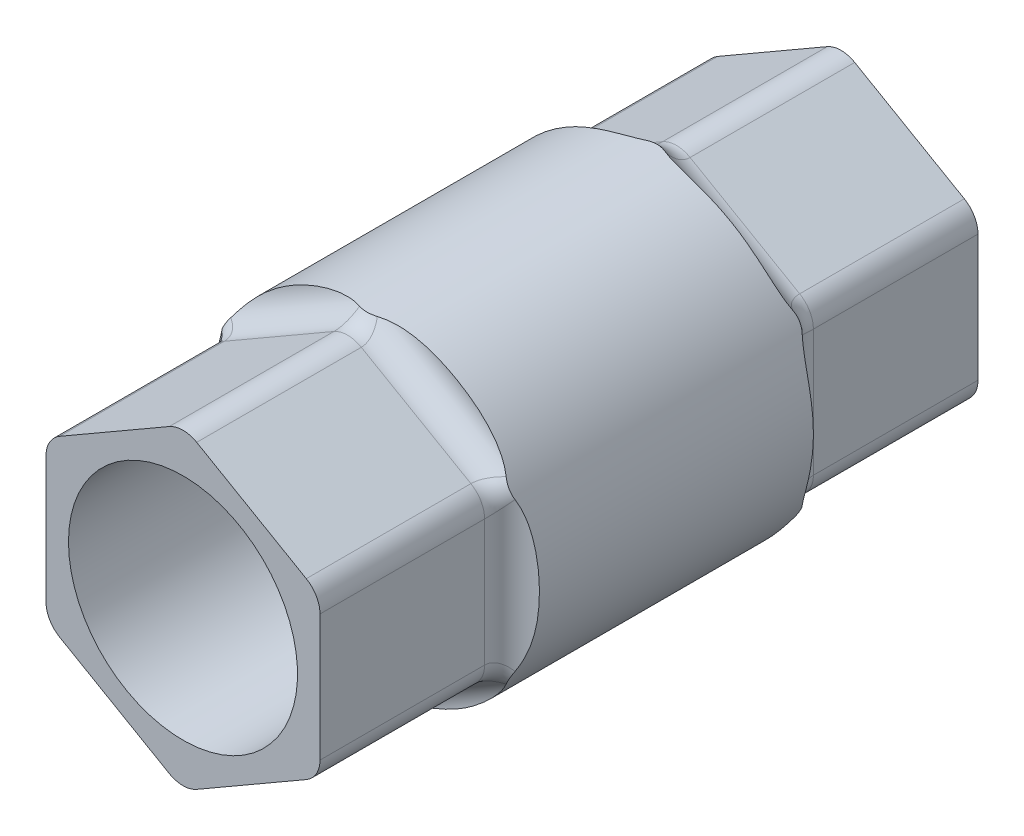
SolidWorks part; units mm, degrees
ref_plane "Front Plane" through (0, 0, 0) normal (0, 0, 1) x (1, 0, 0)
ref_plane "Top Plane" through (0, 0, 0) normal (0, 1, 0) x (1, 0, 0)
ref_plane "Right Plane" through (0, 0, 0) normal (1, 0, 0) x (0, 0, -1)
sketch "Sketch1" plane through (0, 0, 0) normal (0, 0, 1) x (1, 0, 0)
  line L1 (0, 14.6647) -> (-12.7, 7.3323)
  line L2 (-12.7, 7.3323) -> (-12.7, -7.3323)
  line L3 (-12.7, -7.3323) -> (0, -14.6647)
  line L4 (0, -14.6647) -> (12.7, -7.3323)
  line L5 (12.7, -7.3323) -> (12.7, 7.3323)
  line L6 (12.7, 7.3323) -> (0, 14.6647)
  circle A0 centre (0, 0) radius 12.7 construction
  circle A1 centre (0, 0) radius 10.6171
  dimension "D1" = 25.4
  dimension "D2" = 21.2341
extrude "Boss-Extrude1" add sketch "Sketch1" along normal blind 61
ref_plane "Plane1" through (0, 0, 30.5) normal (0, 0, 1) x (1, 0, 0)
sketch "Sketch2" plane through (0, 0, 30.5) normal (0, 0, 1) x (1, 0, 0)
  circle A0 centre (0, 0) radius 10.6171
  circle A1 centre (0, 0) radius 15.24
  dimension "D1" = 30.48
extrude "Boss-Extrude2" add sketch "Sketch2" along normal mid plane 25.4
fillet "Fillet1" radius 2.54 12 edges at (-6.35, -10.9985, 17.8) (6.35, -10.9985, 17.8) (12.7, 0, 17.8) (6.35, 10.9985, 17.8) (-6.35, 10.9985, 17.8) (-12.7, 0, 17.8) (-12.7, 0, 43.2) (-6.35, -10.9985, 43.2) (6.35, -10.9985, 43.2) (12.7, 0, 43.2) (6.35, 10.9985, 43.2) (-6.35, 10.9985, 43.2)
fillet "Fillet2" radius 2.54 24 edges at (-12.8278, 7.4061, 44.9445) (-12.8278, -7.4061, 44.9445) (0, -14.8122, 44.9445) (12.8278, -7.4061, 44.9445) (0, 14.8122, 44.9445) (12.8278, 7.4061, 44.9445) (12.8278, -7.4061, 16.0555) (0, -14.8122, 16.0555) (-12.8278, -7.4061, 16.0555) (-12.8278, 7.4061, 16.0555) (0, 14.8122, 16.0555) (12.8278, 7.4061, 16.0555) (-12.7, 7.3323, 53.37) (-12.7, -7.3323, 53.37) (0, -14.6647, 53.37) (12.7, -7.3323, 53.37) (0, 14.6647, 53.37) (12.7, 7.3323, 53.37) (12.7, -7.3323, 7.63) (0, -14.6647, 7.63) (-12.7, -7.3323, 7.63) (-12.7, 7.3323, 7.63) (0, 14.6647, 7.63) (12.7, 7.3323, 7.63)
